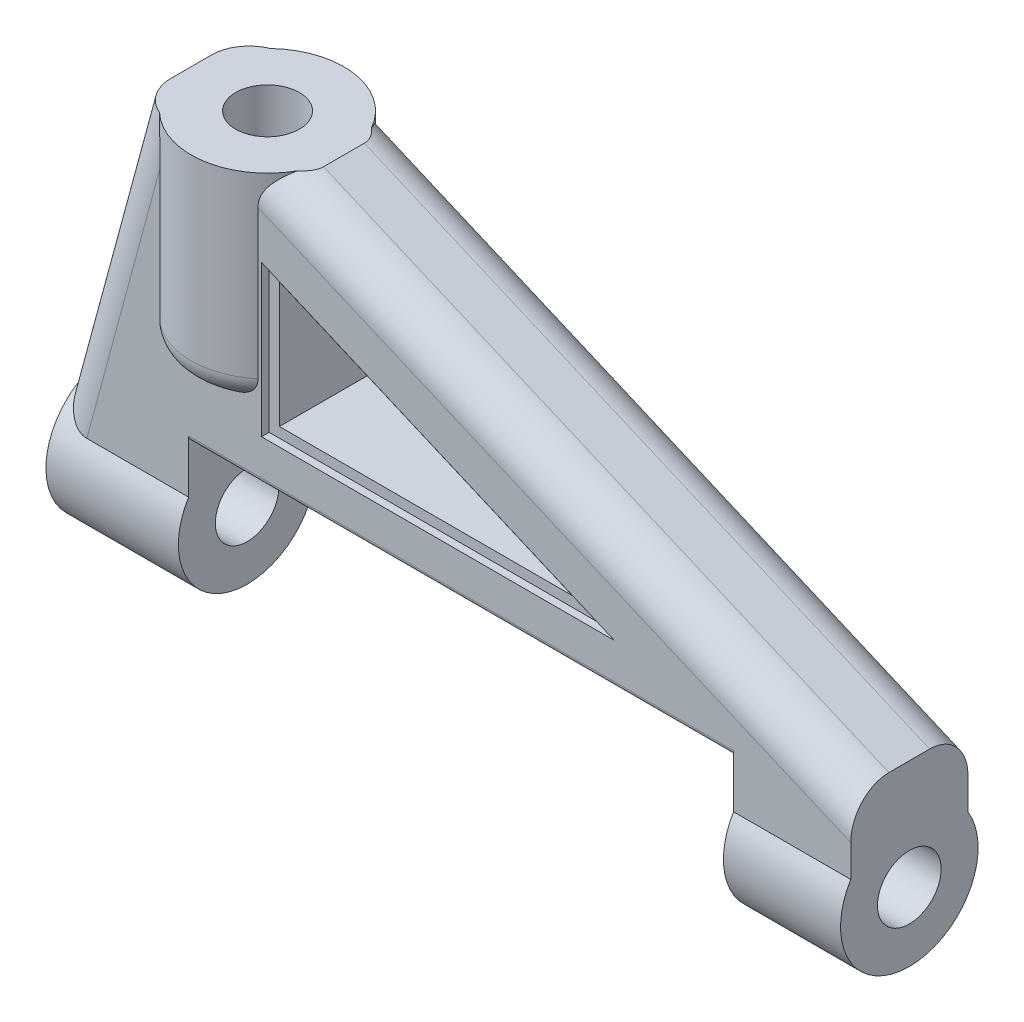
SolidWorks part; units mm, degrees
ref_plane "前视基准面" through (0, 0, 0) normal (0, 0, 1) x (1, 0, 0)
ref_plane "上视基准面" through (0, 0, 0) normal (0, 1, 0) x (1, 0, 0)
ref_plane "右视基准面" through (0, 0, 0) normal (1, 0, 0) x (0, 0, -1)
sketch "草图1" plane through (0, 0, 0) normal (0, 0, 1) x (1, 0, 0)
  line L0 (-27.2562, 0) -> (31.8366, 0) construction
  line L1 (0, 0) -> (0, 28.9871) construction
  line L2 (-0.8, -2.7) -> (-0.8, 3.3)
  line L3 (-3, 13.8) -> (3, 13.8)
  line L4 (3, 13.8) -> (25.2, 4.3)
  line L5 (25.2, 4.3) -> (25.2, -2.7)
  line L6 (25.2, -2.7) -> (20.6, -2.7)
  line L7 (-6, -2.7) -> (-6, 2.7)
  line L8 (-6, 2.7) -> (-3, 13.8)
  line L9 (-0.8, 3.3) -> (20.6, 3.3)
  line L10 (20.6, 3.3) -> (20.6, -2.7)
  line L11 (-0.8, -2.7) -> (-6, -2.7)
  line L12 (2.4668, 10.2212) -> (2.4668, 5.3)
  line L13 (2.4668, 5.3) -> (13.9668, 5.3)
  line L14 (13.9668, 5.3) -> (2.4668, 10.2212)
  dimension "D1" = 5.4
  dimension "D2" = 6
  dimension "D3" = 5.2
  dimension "D4" = 4.6
  dimension "D5" = 31.2
  dimension "D6" = 6
  dimension "D7" = 13.8
  dimension "D8" = 7
  dimension "D9" = 6
  dimension "D10" = 3.5
  dimension "D11" = 2
  dimension "D12" = 11.5
extrude "凸台-拉伸1" add sketch "草图1" along normal blind 4.6
sketch "草图2" plane through (0, 13.8, 0) normal (0, 1, 0) x (1, 0, 0)
  line L0 (-3, 0) -> (3, -4.6) construction
  line L1 (-3, -4.6) -> (3, 0) construction
  line L2 (3, -4.6) -> (3, 0) construction
  circle A0 centre (0, -2.3) radius 3
extrude "凸台-拉伸2" add sketch "草图2" against normal blind 8
sketch "草图3" plane through (-6, 0, 0) normal (-1, 0, 0) x (0, 0, 1)
  line L0 (4.6, 2.7) -> (0, -2.7) construction
  line L1 (0, 2.7) -> (4.6, -2.7) construction
  line L2 (4.6, -2.7) -> (0, -2.7) construction
  circle A0 centre (2.3, 0) radius 2.7
extrude "凸台-拉伸3" add sketch "草图3" against normal up to surface (5.2 mm away) up to face at (-0.8, 0.3, 2.3)
sketch "草图5" plane through (20.6, 0, 0) normal (-1, 0, 0) x (0, 0, 1)
  circle A1 centre (2.3, 0) radius 2.7
  circle A2 centre (2.3, 0) radius 2.7
  dimension "D1" = 0
extrude "凸台-拉伸4" add sketch "草图5" against normal up to surface (4.6 mm away) up to face at (25.2, 0.8, 2.3)
sketch "草图4" plane through (-6, 0, 0) normal (-1, 0, 0) x (0, 0, 1)
  line L0 (0, -1.4142) -> (0, -2.7) construction
  line L1 (4.6, -2.7) -> (0, -2.7) construction
  line L2 (4.6, -1.4142) -> (4.6, -2.7) construction
  line L3 (0, -1.4142) -> (0, -2.7)
  line L4 (4.6, -2.7) -> (0, -2.7)
  line L5 (4.6, -1.4142) -> (4.6, -2.7)
  arc A0 (4.6, -1.4142) -> (4.6, 1.4142) centre (2.3, 0) ccw construction
  arc A1 (0, -1.4142) -> (4.6, -1.4142) centre (2.3, 0) ccw
  line M1 (0, -1.4142) -> (0, -2.7)
  line M2 (0, -2.7) -> (4.6, -2.7)
  line M3 (4.6, -2.7) -> (4.6, -1.4142)
extrude "切除-拉伸1" cut sketch "草图4" against normal through all contours A1 L4 M3 | A1 M1 M2 region at (-6, -2.3375, 0.5441) region at (-6, -2.3375, 4.0559)
fillet "圆角1" radius 1.5 4 edges at (-4.5, 8.25, 0) (-4.5, 8.25, 4.6) (14.1, 9.05, 0) (14.1, 9.05, 4.6)
sketch "草图6" plane through (0, 0, 4.6) normal (0, 0, 1) x (1, 0, 0)
  line L0 (13.9668, 5.3) -> (2.4668, 10.2212) construction
  line L1 (2.4668, 10.2212) -> (2.4668, 5.3) construction
  line L2 (2.4668, 5.3) -> (13.9668, 5.3) construction
  line L3 (13.9668, 5.3) -> (2.4668, 10.2212)
  line L4 (2.4668, 10.2212) -> (2.4668, 5.3)
  line L5 (2.4668, 5.3) -> (13.9668, 5.3)
extrude "切除-拉伸2" cut sketch "草图6" against normal through all
sketch "草图7" plane through (0, 0, 4.6) normal (0, 0, 1) x (1, 0, 0)
  line L0 (2.4668, 10.2212) -> (2.4668, 5.3) construction
  line L1 (13.9668, 5.3) -> (2.4668, 10.2212) construction
  line L2 (2.4668, 5.3) -> (13.9668, 5.3) construction
  line L3 (2.4668, 10.2212) -> (2.4668, 5.3)
  line L4 (13.9668, 5.3) -> (2.4668, 10.2212)
  line L5 (2.4668, 5.3) -> (13.9668, 5.3)
  line L6 (2.0668, 10.8274) -> (2.0668, 4.9)
  line L7 (2.0668, 4.9) -> (15.9183, 4.9)
  line L8 (15.9183, 4.9) -> (2.0668, 10.8274)
  dimension "D1" = 0.4
extrude "切除-拉伸3" cut sketch "草图7" against normal blind 0.3
sketch "草图8" plane through (0, 0, 0) normal (0, 0, -1) x (-1, 0, 0)
  line L3 (-2.0668, 4.9) -> (-2.0668, 10.8274)
  line L4 (-15.9183, 4.9) -> (-2.0668, 4.9)
  line L5 (-2.0668, 10.8274) -> (-15.9183, 4.9)
  line L6 (-2.0668, 4.9) -> (-2.0668, 10.8274)
  line L7 (-15.9183, 4.9) -> (-2.0668, 4.9)
  line L8 (-2.0668, 10.8274) -> (-15.9183, 4.9)
  line L9 (-2.4668, 5.3) -> (-2.4668, 10.2212)
  line L10 (-13.9668, 5.3) -> (-2.4668, 5.3)
  line L11 (-2.4668, 10.2212) -> (-13.9668, 5.3)
  line L12 (-2.4668, 5.3) -> (-2.4668, 10.2212)
  line L13 (-13.9668, 5.3) -> (-2.4668, 5.3)
  line L14 (-2.4668, 10.2212) -> (-13.9668, 5.3)
  dimension "D1" = 0
  dimension "D2" = 0
extrude "切除-拉伸4" cut sketch "草图8" against normal blind 0.3
fillet "圆角2" radius 0.2 2 edges at (9.9, 3.3, 4.6) (9.9, 3.3, 0)
fillet "圆角3" radius 1 2 edges at (0, 5.8, 5.3) (0, 5.8, -0.7)
sketch "草图9" plane through (-6, 0, 0) normal (-1, 0, 0) x (0, 0, 1)
  circle A0 centre (2.3, 0) radius 1.25
  dimension "D1" = 2.5
extrude "切除-拉伸5" cut sketch "草图9" against normal through all
hole_wizard "M3 螺纹孔1" positions "3D草图1" profile "草图11" tap size "M3" standard "GB"
sketch3d "3D草图1"
  line L0 (0, 6.8, 2.3) -> (0, 13.8, 2.3) construction
  point P0 (0, 13.8, 2.3)
sketch "草图11" plane through (0, 13.8, 2.3) normal (1, 0, 0) x (0, 0, 1)
  line L0 (0, 0) -> (0, 7.2511)
  line L1 (0, 7.2511) -> (1.25, 6.5)
  line L2 (1.25, 6.5) -> (1.25, 0)
  line L5 (1.25, 0) -> (0, 0)
  line L10 (0, 7.2511) -> (-1.25, 6.5) construction
  line L11 (0, -6.35) -> (0, 107.95) construction
  dimension "螺纹孔钻头直径" = 2.5
  dimension "螺纹孔钻头深度" = 6.5
  dimension "导头角度" = 118
cosmetic thread "孔螺蚊线1" parameters "D1"=4, "D2"=3
equation "\"4。6\"=6.91335"
